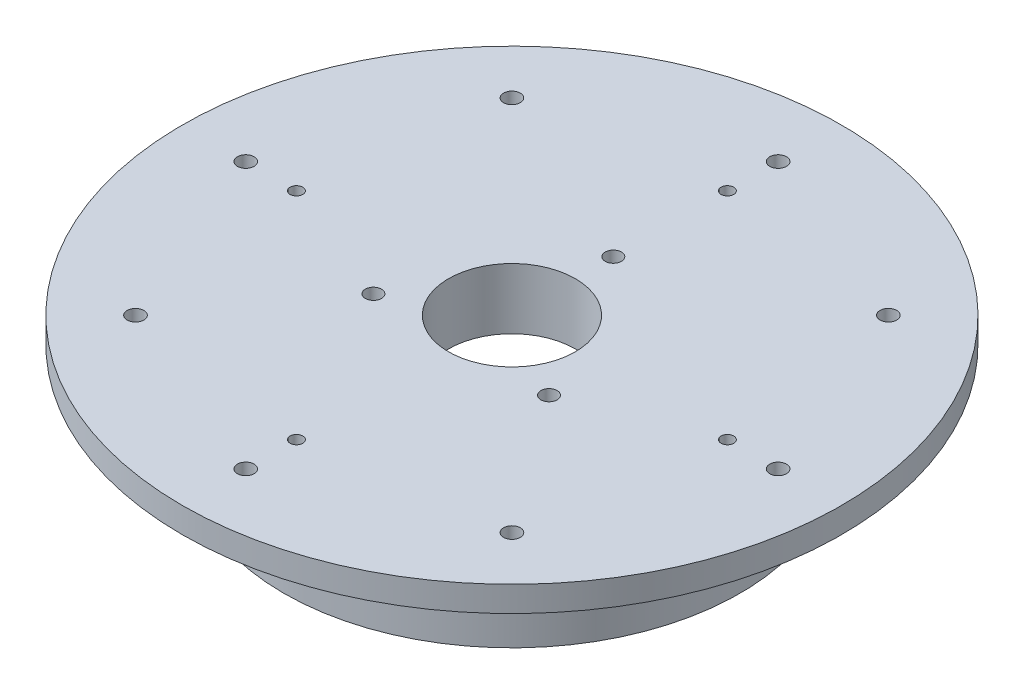
SolidWorks part; units mm, degrees
material "7079 合金"
ref_plane "前视基准面" through (0, 0, 0) normal (0, 0, 1) x (1, 0, 0)
ref_plane "上视基准面" through (0, 0, 0) normal (0, 1, 0) x (1, 0, 0)
ref_plane "右视基准面" through (0, 0, 0) normal (1, 0, 0) x (0, 0, -1)
other "Configuration Table"
sketch "草图1" plane through (0, 0, 0) normal (0, 1, 0) x (1, 0, 0)
  circle A0 centre (0, 0) radius 65
  dimension "D1" = 130
extrude "凸台-拉伸1" add sketch "草图1" along normal blind 5
sketch "草图2" plane through (0, 0, 0) normal (0, -1, 0) x (-1, 0, 0)
  circle A0 centre (0, 0) radius 50
  dimension "D1" = 100
extrude "凸台-拉伸2" add sketch "草图2" along normal blind 7
sketch "草图3" plane through (0, 5, 0) normal (0, 1, 0) x (1, 0, 0)
  circle A0 centre (0, 0) radius 20 construction
  circle A1 centre (0, 20) radius 1.6
  circle A2 centre (17.3205, -10) radius 1.6
  circle A3 centre (-17.3205, -10) radius 1.6
  point P11 (0, 0)
  dimension "D1" = 40
  dimension "D2" = 3.2
  dimension "D3" = 3
extrude "切除-拉伸1" cut sketch "草图3" against normal blind 58
sketch "草图4" plane through (0, -7, 0) normal (0, -1, 0) x (-1, 0, 0)
  circle A0 centre (0, 0) radius 12.5
  dimension "D1" = 25
extrude "切除-拉伸2" cut sketch "草图4" against normal through all
sketch "草图5" plane through (0, -7, 0) normal (0, -1, 0) x (-1, 0, 0)
  circle A0 centre (0, 0) radius 40
  circle A1 centre (0, 0) radius 45
  dimension "D1" = 80
  dimension "D2" = 90
extrude "凸台-拉伸3" add sketch "草图5" along normal blind 13
sketch "草图6" plane through (0, -20, 0) normal (0, -1, 0) x (-1, 0, 0)
  circle A0 centre (0, 0) radius 42.5 construction
  circle A3 centre (0, -42.5) radius 1.6
  circle A4 centre (-42.5, 0) radius 1.6
  circle A5 centre (0, 42.5) radius 1.6
  circle A6 centre (42.5, 0) radius 1.6
  point P14 (0, 0)
  dimension "D1" = 85
  dimension "D2" = 3.2
  dimension "D3" = 4
hole_wizard "M3 螺纹孔1" positions "3D草图2" profile "草图8" tap size "M3" standard "GB" end condition through all
sketch3d "3D草图2"
  point P0 (0, -20, 42.5)
  point P3 (-42.5, -20, 0)
  point P6 (0, -20, -42.5)
  point P9 (42.5, -20, 0)
sketch "草图8" plane through (0, -20, 42.5) normal (1, 0, 0) x (0, 0, -1)
  line L0 (0, 0) -> (0, 25)
  line L1 (0, 25) -> (1.25, 25)
  line L2 (1.25, 25) -> (1.25, 0)
  line L5 (1.25, 0) -> (0, 0)
  line L11 (0, -6.35) -> (0, 107.95) construction
  dimension "通孔螺纹孔钻头直径" = 2.5
  dimension "通孔螺纹孔钻头深度" = 25
cosmetic thread "孔螺蚊线1" parameters "D2"=3
cosmetic thread "孔螺蚊线2" parameters "D2"=3
cosmetic thread "孔螺蚊线3" parameters "D2"=3
cosmetic thread "孔螺蚊线4" parameters "D2"=3
sketch "草图9" plane through (0, 5, 0) normal (0, 1, 0) x (1, 0, 0)
  circle A0 centre (0, 0) radius 52.5 construction
  circle A1 centre (0, 52.5) radius 1.6
  circle A2 centre (37.1231, 37.1231) radius 1.6
  circle A3 centre (52.5, 0) radius 1.6
  circle A4 centre (37.1231, -37.1231) radius 1.6
  circle A5 centre (0, -52.5) radius 1.6
  circle A6 centre (-37.1231, -37.1231) radius 1.6
  circle A7 centre (-52.5, 0) radius 1.6
  circle A8 centre (-37.1231, 37.1231) radius 1.6
  point P21 (0, 0)
  dimension "D1" = 105
  dimension "D2" = 3.2
  dimension "D3" = 8
extrude "切除-拉伸3" cut sketch "草图9" against normal blind 10
hole_wizard "M4 螺纹孔3" positions "3D草图5" profile "草图12" tap size "M4" standard "GB"
sketch3d "3D草图5"
  line L0 (0, 0, -52.5) -> (0, 5, -52.5) construction
  line L1 (37.1231, 0, -37.1231) -> (37.1231, 5, -37.1231) construction
  line L2 (52.5, 0, 0) -> (52.5, 5, 0) construction
  line L3 (37.1231, 0, 37.1231) -> (37.1231, 5, 37.1231) construction
  line L4 (0, 0, 52.5) -> (0, 5, 52.5) construction
  line L5 (-37.1231, 0, 37.1231) -> (-37.1231, 5, 37.1231) construction
  line L6 (-52.5, 0, 0) -> (-52.5, 5, 0) construction
  line L7 (-37.1231, 0, -37.1231) -> (-37.1231, 5, -37.1231) construction
  point P0 (0, 5, -52.5)
  point P4 (37.1231, 5, -37.1231)
  point P8 (52.5, 5, 0)
  point P12 (37.1231, 5, 37.1231)
  point P16 (0, 5, 52.5)
  point P20 (-37.1231, 5, 37.1231)
  point P24 (-52.5, 5, 0)
  point P28 (-37.1231, 5, -37.1231)
cosmetic thread "孔螺蚊线5" parameters "D1"=6, "D2"=4
cosmetic thread "孔螺蚊线6" parameters "D1"=6, "D2"=4
cosmetic thread "孔螺蚊线7" parameters "D1"=6, "D2"=4
cosmetic thread "孔螺蚊线8" parameters "D1"=6, "D2"=4
cosmetic thread "孔螺蚊线9" parameters "D1"=6, "D2"=4
cosmetic thread "孔螺蚊线10" parameters "D1"=6, "D2"=4
cosmetic thread "孔螺蚊线11" parameters "D1"=6, "D2"=4
cosmetic thread "孔螺蚊线12" parameters "D1"=6, "D2"=4
sketch "草图12" plane through (0, 5, -52.5) normal (1, 0, 0) x (0, 0, 1)
  line L0 (0, 0) -> (0, 10.4914)
  line L1 (0, 10.4914) -> (1.65, 9.5)
  line L2 (1.65, 9.5) -> (1.65, 0)
  line L5 (1.65, 0) -> (0, 0)
  line L10 (0, 10.4914) -> (-1.65, 9.5) construction
  line L11 (0, -6.35) -> (0, 107.95) construction
  dimension "螺纹孔钻头直径" = 3.3
  dimension "螺纹孔钻头深度" = 9.5
  dimension "导头角度" = 118
